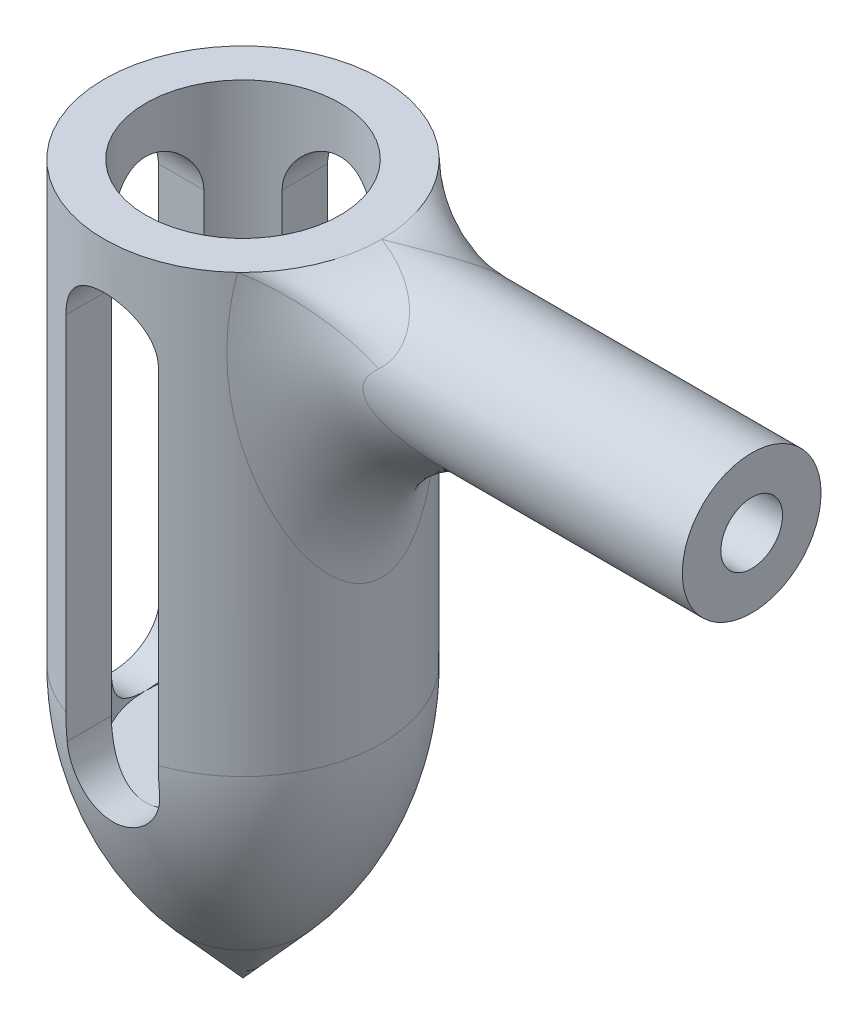
SolidWorks part; units mm, degrees
material "ABS"
ref_plane "Front Plane" through (0, 0, 0) normal (0, 0, 1) x (1, 0, 0)
ref_plane "Top Plane" through (0, 0, 0) normal (0, 1, 0) x (1, 0, 0)
ref_plane "Right Plane" through (0, 0, 0) normal (1, 0, 0) x (0, 0, -1)
sketch "Sketch7" plane through (0, 0, 0) normal (0, 1, 0) x (1, 0, 0)
  circle A0 centre (0, 0) radius 4.5
  dimension "D1" = 9
extrude "Boss-Extrude4" add sketch "Sketch7" against normal blind 18
sketch "Sketch8" plane through (0, 0, 0) normal (0, 1, 0) x (1, 0, 0)
  circle A0 centre (0, 0) radius 3.15
  dimension "D1" = 6.3
sketch "Sketch11" plane through (0, 0, 0) normal (0, 0, 1) x (1, 0, 0)
  line L0 (0, -18) -> (0, -26.896) construction
  line L1 (0, -23) -> (4.5, -18)
  line L2 (4.5, -18) -> (0, -18)
  line L3 (0, -18) -> (0, -23)
  line L4 (-4.5, -18) -> (4.5, -18) construction
  dimension "D1" = 4.5
  dimension "D2" = 5
revolve "Revolve2" add sketch "Sketch11" angle 360 about L0
sketch "Sketch12" plane through (0, 0, 0) normal (1, 0, 0) x (0, 0, -1)
  line L2 (4.5, 0) -> (-4.5, 0) construction
  circle A1 centre (0, -2.25) radius 2.25
  dimension "D1" = 4.5
extrude "Boss-Extrude5" add sketch "Sketch12" along normal blind 16.5
extrude "Cut-Extrude2" cut sketch "Sketch8" against normal blind 16.5
sketch "Sketch13" plane through (0, 0, 0) normal (0, 0, 1) x (1, 0, 0)
  line L0 (0, -15) -> (0, -3) construction
  line L1 (-1.5, -15) -> (-1.5, -3)
  line L2 (1.5, -15) -> (1.5, -3)
  line L3 (4.5, -18) -> (-4.5, -18) construction
  line L4 (4.5, 0) -> (-4.5, 0) construction
  arc A0 (-1.5, -15) -> (1.5, -15) centre (0, -15) ccw
  arc A1 (1.5, -3) -> (-1.5, -3) centre (0, -3) ccw
  point P3 (0, -9)
  dimension "D1" = 3
  dimension "D3" = 1.5
  dimension "D2" = 3
extrude "Cut-Extrude3" cut sketch "Sketch13" against normal blind 10
pattern_circular "CirPattern1" count 3 over 180 about axis through (0, 0, 0) along (0, 1, 0) of "Cut-Extrude3"
fillet "Fillet1" radius 5 1 edges at (4.4943, -4.4885, 0.227)
sketch "Sketch14" plane through (16.5, 0, 0) normal (1, 0, 0) x (0, 0, -1)
  circle A0 centre (0, -2.25) radius 1
  dimension "D1" = 2
extrude "Cut-Extrude4" cut sketch "Sketch14" against normal blind 10
fillet "Fillet2" radius 10 1 edges at (0, -18, 4.5)
